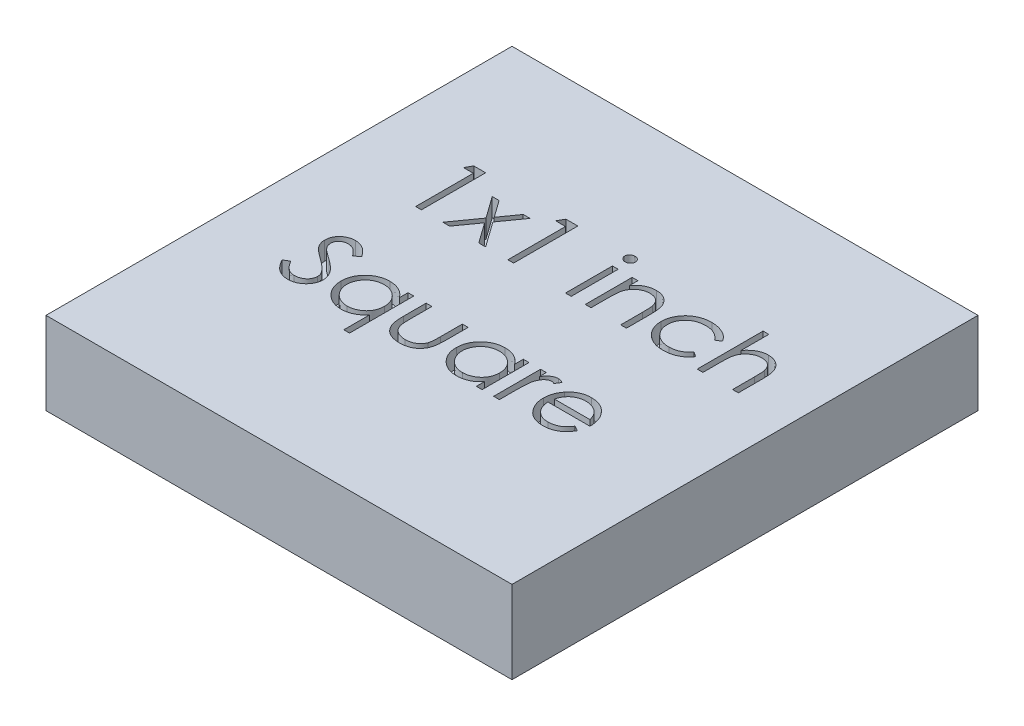
SolidWorks part; units mm, degrees
ref_plane "Front Plane" through (0, 0, 0) normal (0, 0, 1) x (1, 0, 0)
ref_plane "Top Plane" through (0, 0, 0) normal (0, 1, 0) x (1, 0, 0)
ref_plane "Right Plane" through (0, 0, 0) normal (1, 0, 0) x (0, 0, -1)
sketch "Sketch1" plane through (0, 0, 0) normal (0, 1, 0) x (1, 0, 0)
  line L1 (12.7, -12.7) -> (-12.7, -12.7)
  line L2 (12.7, -12.7) -> (12.7, 12.7)
  line L3 (12.7, 12.7) -> (-12.7, 12.7)
  line L4 (-12.7, -12.7) -> (-12.7, 12.7)
  line L5 (12.7, -12.7) -> (-12.7, 12.7) construction
  line L6 (12.7, 12.7) -> (-12.7, -12.7) construction
  point P0 (0, 0)
  dimension "D1" = 25.4
  dimension "D2" = 25.4
extrude "Boss-Extrude1" add sketch "Sketch1" along normal blind 4.5
sketch "Sketch2" plane through (0, 4.5, 0) normal (0, 1, 0) x (1, 0, 0)
  text T0 "1x1 inch\r\nSquare"
extrude "Cut-Extrude1" cut sketch "Sketch2" against normal blind 1
